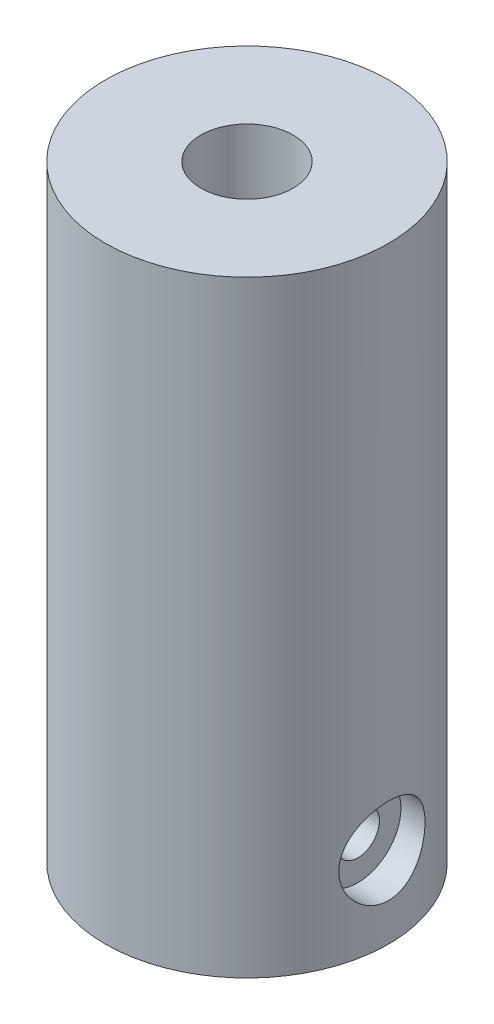
SolidWorks part; units mm, degrees
ref_plane "Front Plane" through (0, 0, 0) normal (0, 0, 1) x (1, 0, 0)
ref_plane "Top Plane" through (0, 0, 0) normal (0, 1, 0) x (1, 0, 0)
ref_plane "Right Plane" through (0, 0, 0) normal (1, 0, 0) x (0, 0, -1)
sketch "Sketch1" plane through (0, 0, 0) normal (0, 1, 0) x (1, 0, 0)
  circle A0 centre (0, 0) radius 8.89
  dimension "D1" = 17.78
extrude "Boss-Extrude1" add sketch "Sketch1" along normal blind 38.1
hole_wizard "Ø3.0mm Dowel Hole2" positions "Sketch2" profile "Sketch3" hole size "Ø3.0" standard "ANSI Metric" end condition through all
sketch "Sketch2" plane through (0, 38.1, 0) normal (0, 1, 0) x (1, 0, 0)
  point P0 (0, 0)
sketch "Sketch3" plane through (0, 38.1, 0) normal (1, 0, 0) x (0, 0, 1)
  line L0 (0, 0) -> (0, 38.1)
  line L1 (0, 38.1) -> (1.75, 38.1)
  line L2 (1.75, 38.1) -> (1.75, 0)
  line L5 (1.75, 0) -> (0, 0)
  line L11 (0, -6.35) -> (0, 107.95) construction
  dimension "Thru Hole Dia." = 3.5
  dimension "Thru Hole Depth" = 38.1
sketch "Sketch4" plane through (0, 0, 0) normal (1, 0, 0) x (0, 0, -1)
  line L0 (-8.89, 38.1) -> (-8.89, 0) construction
  line L1 (-8.89, 34.925) -> (-5.08, 34.925)
  line L2 (-8.89, 34.925) -> (-8.89, 3.175)
  line L3 (-8.89, 3.175) -> (-5.08, 3.175)
  line L4 (-5.08, 34.925) -> (-5.08, 3.175)
  line L5 (-8.89, 0) -> (8.89, 0) construction
  line L6 (8.89, 38.1) -> (-8.89, 38.1) construction
  line L7 (0, 0) -> (0, 26.8631) construction
  dimension "D1" = 3.175
  dimension "D2" = 3.175
  dimension "D3" = 3.81
ref_plane "Plane1" through (8.89, 0, 0) normal (1, 0, 0) x (0, 0, -1)
sketch "Sketch5" plane through (8.89, 0, 0) normal (1, 0, 0) x (0, 0, -1)
  line L0 (1.75, 38.1) -> (-1.75, 38.1) construction
  circle A0 centre (0, 33.02) radius 1.27
  circle A1 centre (0, 5.08) radius 1.27
  dimension "D3" = 2.54
  dimension "D1" = 5.08
  dimension "D2" = 5.08
hole_wizard "CBORE for #2 Button Head Cap Screw1" positions "Sketch6" profile "Sketch7" counterbore size "#2" standard "ANSI Inch" end condition up to next
sketch "Sketch6" plane through (8.89, 0, 0) normal (1, 0, 0) x (0, 0, -1)
  point P3 (0, 5.08)
sketch "Sketch7" plane through (8.89, 5.08, 0) normal (0, 1, 0) x (0, 0, -1)
  line L0 (0, 0) -> (0, 7.14)
  line L1 (0, 7.14) -> (1.3525, 7.14)
  line L3 (1.3525, 7.14) -> (1.3526, 1.9304)
  line L4 (1.3526, 1.9304) -> (2.7064, 1.9304)
  line L5 (2.7064, 1.9304) -> (2.7064, 0)
  line L7 (2.7064, 0) -> (0, 0)
  line L11 (0, -6.35) -> (0, 107.95) construction
  dimension "Thru Hole Dia." = 2.7051
  dimension "Thru Hole Depth" = 7.14
  dimension "C'Bore Dia." = 5.4127
  dimension "C'Bore Depth" = 1.9304
hole_wizard "#12 Clearance Hole1" positions "Sketch9" profile "Sketch10" hole size "#12" standard "ANSI Inch"
sketch "Sketch9" plane through (0, 38.1, 0) normal (0, 1, 0) x (1, 0, 0)
  point P0 (0, 0)
sketch "Sketch10" plane through (0, 38.1, 0) normal (1, 0, 0) x (0, 0, 1)
  line L0 (0, 0) -> (0, 20.7899)
  line L1 (0, 20.7899) -> (2.8956, 19.05)
  line L2 (2.8956, 19.05) -> (2.8956, 0)
  line L5 (2.8956, 0) -> (0, 0)
  line L10 (0, 20.7899) -> (-2.8956, 19.05) construction
  line L11 (0, -6.35) -> (0, 107.95) construction
  dimension "Hole Dia." = 5.7912
  dimension "Hole Depth" = 19.05
  dimension "Drill Angle" = 118
sketch "Sketch8" plane through (0, 0, 0) normal (0, -1, 0) x (1, 0, 0)
  circle A0 centre (0, 0) radius 2.75
  circle A1 centre (0, 0) radius 7.39
  circle A2 centre (0, 0) radius 1.75 construction
  circle A3 centre (0, 0) radius 8.89 construction
  dimension "D1" = 1
  dimension "D2" = 1.5
extrude "Cut-Extrude1" [suppressed] cut sketch "Sketch8" against normal blind 2.54
